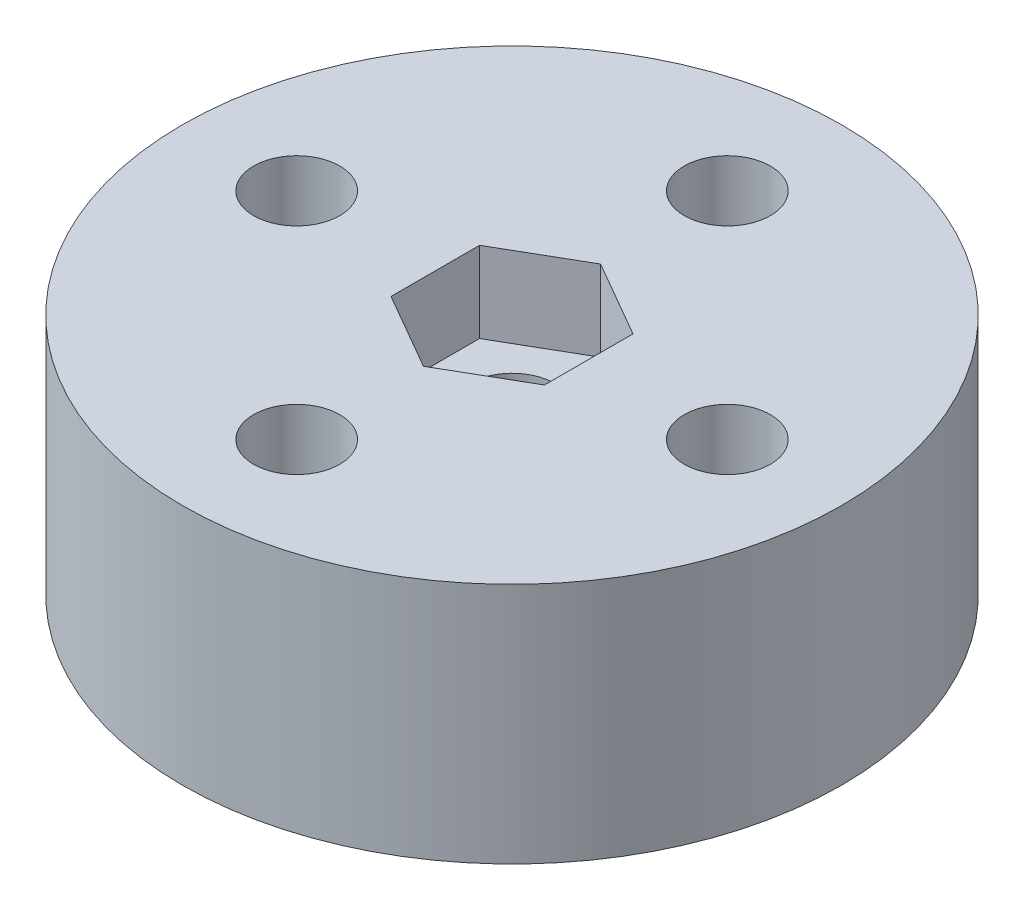
SolidWorks part; units mm, degrees
ref_plane "前视基准面" through (0, 0, 0) normal (0, 0, 1) x (1, 0, 0)
ref_plane "上视基准面" through (0, 0, 0) normal (0, 1, 0) x (1, 0, 0)
ref_plane "右视基准面" through (0, 0, 0) normal (1, 0, 0) x (0, 0, -1)
sketch "草图1" plane through (0, 0, 0) normal (0, 1, 0) x (1, 0, 0)
  line L1 (0, -3.2909) -> (2.85, -1.6454)
  line L2 (2.85, -1.6454) -> (2.85, 1.6454)
  line L3 (2.85, 1.6454) -> (0, 3.2909)
  line L4 (0, 3.2909) -> (-2.85, 1.6454)
  line L5 (-2.85, 1.6454) -> (-2.85, -1.6454)
  line L6 (-2.85, -1.6454) -> (0, -3.2909)
  circle A0 centre (0, 0) radius 12.25
  circle A1 centre (0, 0) radius 8 construction
  circle A2 centre (0, 8) radius 1.6
  circle A3 centre (8, 0) radius 1.6
  circle A4 centre (0, -8) radius 1.6
  circle A5 centre (-8, 0) radius 1.6
  circle A6 centre (0, 0) radius 2.85 construction
  circle A7 centre (0, 0) radius 1.6
  point P15 (0, 0)
  dimension "D1" = 24.5
  dimension "D2" = 4
  dimension "D3" = 5.7
extrude "凸台-拉伸1" add sketch "草图1" against normal blind 3 contours A0 A5 A4 A3 A2 L6 L5 L4 L3 L2 L1 | L5 L6 L1 L2 L3 L4 A7 region at (-1.3815, 0, 2.3928) region at (-11.9035, 0, 0)
extrude "凸台-拉伸2" add sketch "草图1<3>" along normal blind 3 contours A0 A5 A4 A3 A2 L6 L5 L4 L3 L2 L1 region at (-11.9035, 0, 0)
sketch "草图1<3>" plane through (0, 0, 0) normal (0, 1, 0) x (1, 0, 0) same geometry as "草图1"
extrude "凸台-拉伸3" add sketch "草图1<4>" along normal blind 3 contours L5 L6 L1 L2 L3 L4 A7 region at (-1.3815, 0, 2.3928)
sketch "草图1<4>" plane through (0, 0, 0) normal (0, 1, 0) x (1, 0, 0) same geometry as "草图1"
extrude "凸台-拉伸4" add sketch "草图1<5>" along normal blind 3 from surface contours A0 A5 A4 A3 A2 L6 L5 L4 L3 L2 L1 region at (-11.9035, 0, 0) starting at face at (-8, 3, 1.6)
sketch "草图1<5>" plane through (0, 0, 0) normal (0, 1, 0) x (1, 0, 0) same geometry as "草图1"
